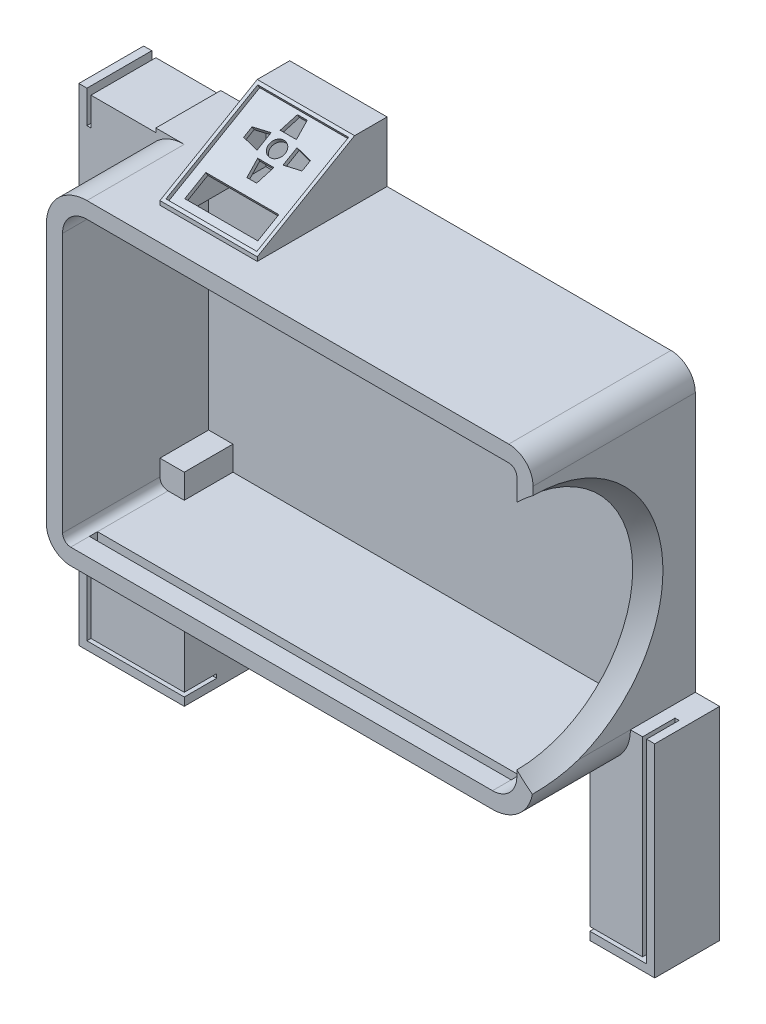
SolidWorks part; units mm, degrees
ref_plane "Front Plane" through (0, 0, 0) normal (0, 0, 1) x (1, 0, 0)
ref_plane "Top Plane" through (0, 0, 0) normal (0, 1, 0) x (1, 0, 0)
ref_plane "Right Plane" through (0, 0, 0) normal (1, 0, 0) x (0, 0, -1)
sketch "Sketch1" plane through (0, 0, 0) normal (0, 0, 1) x (1, 0, 0)
  line L1 (-190.5, -127) -> (190.5, -127)
  line L2 (-190.5, -127) -> (-190.5, 127)
  line L3 (-190.5, 127) -> (190.5, 127)
  line L4 (190.5, -127) -> (190.5, 127)
  line L5 (-190.5, -127) -> (190.5, 127) construction
  line L6 (-190.5, 127) -> (190.5, -127) construction
  point P0 (0, 0)
  dimension "D1" = 381
  dimension "D2" = 254
extrude "Boss-Extrude1" add sketch "Sketch1" against normal blind 127
fillet "Fillet5" radius 19.05 2 edges at (-190.5, -127, -63.5) (190.5, 127, -63.5)
fillet "Fillet4" radius 31.75 2 edges at (190.5, -127, -63.5) (-190.5, 127, -63.5)
sketch "Sketch3" plane through (0, 0, 0) normal (0, 0, -1) x (-1, 0, 0)
  line L16 (-158.75, -114.3) -> (171.45, -114.3)
  line L17 (-177.8, 107.95) -> (-177.8, -95.25)
  line L18 (158.75, 114.3) -> (-171.45, 114.3)
  line L19 (177.8, -107.95) -> (177.8, 95.25)
  line L20 (-158.75, -114.3) -> (171.45, -114.3)
  line L21 (-177.8, 107.95) -> (-177.8, -95.25)
  line L22 (158.75, 114.3) -> (-171.45, 114.3)
  line L23 (177.8, -107.95) -> (177.8, 95.25)
  arc A13 (-177.8, -95.25) -> (-158.75, -114.3) centre (-158.75, -95.25) ccw
  arc A14 (-171.45, 114.3) -> (-177.8, 107.95) centre (-171.45, 107.95) ccw
  arc A15 (177.8, 95.25) -> (158.75, 114.3) centre (158.75, 95.25) ccw
  arc A16 (171.45, -114.3) -> (177.8, -107.95) centre (171.45, -107.95) ccw
  arc A17 (-177.8, -95.25) -> (-158.75, -114.3) centre (-158.75, -95.25) ccw
  arc A18 (-171.45, 114.3) -> (-177.8, 107.95) centre (-171.45, 107.95) ccw
  arc A19 (177.8, 95.25) -> (158.75, 114.3) centre (158.75, 95.25) ccw
  arc A20 (171.45, -114.3) -> (177.8, -107.95) centre (171.45, -107.95) ccw
  dimension "D1" = 12.7
extrude "Cut-Extrude1" cut sketch "Sketch3" along normal offset from surface (114.3 mm away) 12.7 up to face at (0, 0, -127)
sketch "Sketch5" plane through (0, -127, 0) normal (0, -1, 0) x (1, 0, 0)
  line L0 (158.75, -127) -> (158.75, 0) construction
  line L1 (158.75, -14.605) -> (-171.45, -14.605)
  line L2 (158.75, -14.605) -> (158.75, -20.955)
  line L3 (158.75, -20.955) -> (-171.45, -20.955)
  line L4 (-171.45, -14.605) -> (-171.45, -20.955)
  line L5 (-171.45, 0) -> (-171.45, -127) construction
  line L6 (-171.45, 0) -> (158.75, 0) construction
  dimension "D1" = 6.35
  dimension "D2" = 14.605
extrude "Cut-Extrude2" cut sketch "Sketch5" against normal up to next
ref_plane "Plane1" through (0, 0, 0) normal (0, 1, 0) x (1, 0, 0)
sketch "Sketch6" plane through (0, 0, 0) normal (0, 1, 0) x (1, 0, 0)
  line L0 (139.7, 0) -> (266.7, 0)
  line L1 (171.45, 0) -> (-158.75, 0) construction
  line L2 (266.7, 0) -> (266.7, 127)
  line L3 (171.45, 127) -> (-158.75, 127) construction
  line L4 (190.5, 127) -> (190.5, 0) construction
  arc A0 (139.7, 0) -> (266.7, 127) centre (266.7, 0) cw
  point P7 (277.1595, 123.7315)
  point P10 (248.6882, 127)
  point P13 (139.7, 0)
  point P14 (0, 0)
  dimension "D1" = 76.2
revolve "Cut-Revolve1" cut sketch "Sketch6" angle 360 about L2
sketch "Sketch7" plane through (0, 0, -127) normal (0, 0, -1) x (-1, 0, 0)
  line L0 (190.5, 95.25) -> (190.5, -107.95) construction
  line L1 (158.75, 127) -> (241.3, 127)
  line L2 (158.75, 127) -> (158.75, 50.8)
  line L3 (158.75, 50.8) -> (241.3, 50.8)
  line L4 (241.3, 127) -> (241.3, 50.8)
  line L5 (171.45, -127) -> (-158.75, -127) construction
  line L6 (234.95, 127) -> (231.775, 127)
  line L7 (234.95, 127) -> (234.95, 101.6)
  line L8 (234.95, 101.6) -> (231.775, 101.6)
  line L9 (231.775, 127) -> (231.775, 101.6)
  line L10 (-158.75, -95.25) -> (-209.55, -95.25)
  line L11 (-158.75, -95.25) -> (-158.75, -254)
  line L12 (-158.75, -254) -> (-209.55, -254)
  line L13 (-209.55, -95.25) -> (-209.55, -254)
  line L14 (0, 127) -> (0, -127) construction
  line L15 (-171.45, 127) -> (158.75, 127) construction
  line L16 (158.75, -254) -> (241.3, -254)
  line L17 (241.3, -95.25) -> (241.3, -254)
  line L18 (158.75, -95.25) -> (241.3, -95.25)
  line L19 (158.75, -95.25) -> (158.75, -254)
  line L21 (231.775, 127) -> (180.975, 127)
  line L22 (231.775, 127) -> (231.775, 123.825)
  line L23 (231.775, 123.825) -> (180.975, 123.825)
  line L24 (180.975, 127) -> (180.975, 123.825)
  point P31 (181.2865, 123.825)
  line M11 (190.5, -107.95) -> (190.5, 95.25)
  arc M12 (190.5, 95.25) -> (158.75, 127) centre (158.75, 95.25) ccw
  dimension "D1" = 50.8
  dimension "D2" = 76.2
  dimension "D3" = 3.175
  dimension "D4" = 6.35
  dimension "D5" = 25.4
  dimension "D6" = 50.8
  dimension "D7" = 127
  dimension "D8" = 50.8
extrude "Boss-Extrude2" add sketch "Sketch7" against normal blind 50.8 contours L9 L1 L3 L4 L7 L8 M12 M11 | L16 L17 L18 L19 | L11 L10 L13 L12 region at (-214.1054, 88.5803, -127)
sketch "Sketch8" plane through (0, 0, -76.2) normal (0, 0, 1) x (1, 0, 0)
  line L0 (-234.95, -95.25) -> (-234.95, -247.65)
  line L1 (-190.5, -95.25) -> (-241.3, -95.25) construction
  line L2 (-234.95, -247.65) -> (-158.75, -247.65)
  line L3 (-158.75, -127) -> (-158.75, -254) construction
  line L4 (-158.75, -247.65) -> (-158.75, -244.475)
  line L5 (-158.75, -244.475) -> (-231.775, -244.475)
  line L6 (-231.775, -244.475) -> (-231.775, -95.25)
  line L7 (-231.775, -95.25) -> (-234.95, -95.25)
  line L8 (-234.95, 101.6) -> (-231.775, 101.6) construction
  line L9 (-234.95, 127) -> (-234.95, 101.6) construction
  line L10 (-158.75, -254) -> (-241.3, -254) construction
  line L11 (158.75, -247.65) -> (203.2, -247.65)
  line L12 (158.75, -127) -> (158.75, -254) construction
  line L13 (203.2, -247.65) -> (203.2, -95.25)
  line L14 (190.5, -95.25) -> (209.55, -95.25) construction
  line L15 (203.2, -95.25) -> (200.025, -95.25)
  line L16 (200.025, -95.25) -> (200.025, -244.475)
  line L17 (200.025, -244.475) -> (158.75, -244.475)
  line L18 (158.75, -244.475) -> (158.75, -247.65)
  line L19 (209.55, -95.25) -> (209.55, -254) construction
  point P26 (200.025, -95.25)
  point P27 (201.5135, -95.25)
  dimension "D1" = 6.35
  dimension "D2" = 6.35
extrude "Cut-Extrude3" cut sketch "Sketch8" against normal blind 25.4
ref_plane "Plane2" through (-127, 0, 0) normal (1, 0, 0) x (0, 0, -1)
sketch "Sketch9" plane through (-127, 0, 0) normal (1, 0, 0) x (0, 0, -1)
  line L0 (25.4, 127) -> (25.4, 130.175)
  line L1 (0, 127) -> (127, 127) construction
  line L2 (25.4, 130.175) -> (101.6, 174.1691)
  line L4 (25.4, 127) -> (127, 127)
  line L5 (0, 127) -> (0, 107.95) construction
  line L6 (101.6, 174.1691) -> (127, 174.1691)
  line L7 (127, 174.1691) -> (127, 127)
  line L8 (127, 107.95) -> (127, 127) construction
  point P4 (107.95, 174.4916)
  point P9 (101.6, 127)
  point P11 (0, 0)
  dimension "D1" = 25.4
  dimension "D3" = 25.4
  dimension "D4" = 3.175
  dimension "D5" = 60
extrude "Boss-Extrude3" add sketch "Sketch9" along normal blind 76.2
sketch "Sketch10" plane through (0, 86.6327, 50.0174) normal (0, 0.866, 0.5) x (1, 0, 0)
  line L8 (-124.46, 172.5327) -> (-124.46, 89.6245)
  line L9 (-124.46, 89.6245) -> (-53.34, 89.6245)
  line L10 (-53.34, 89.6245) -> (-53.34, 172.5327)
  line L11 (-53.34, 172.5327) -> (-124.46, 172.5327)
  line L12 (-124.46, 172.5327) -> (-124.46, 89.6245)
  line L13 (-124.46, 89.6245) -> (-53.34, 89.6245)
  line L14 (-53.34, 89.6245) -> (-53.34, 172.5327)
  line L15 (-53.34, 172.5327) -> (-124.46, 172.5327)
  dimension "D1" = 2.54
extrude "Cut-Extrude4" cut sketch "Sketch10" against normal blind 12.7
sketch "Sketch11" plane through (0, 114.3, 0) normal (0, -1, 0) x (1, 0, 0)
  line L0 (-124.46, -33.9497) -> (-53.34, -33.9497) construction
  line L1 (-124.46, -33.9497) -> (-53.34, -33.9497)
  line L2 (-124.46, -33.9497) -> (-124.46, -105.7503)
  line L3 (-124.46, -105.7503) -> (-53.34, -105.7503)
  line L4 (-53.34, -33.9497) -> (-53.34, -105.7503)
  line L5 (-124.46, -105.7503) -> (-124.46, -33.9497) construction
  line L6 (-53.34, -105.7503) -> (-124.46, -105.7503) construction
  line L7 (-53.34, -33.9497) -> (-53.34, -105.7503) construction
extrude "Cut-Extrude5" cut sketch "Sketch11" against normal up to surface (6.1465 mm away) up to face at (-88.9, 141.1735, -69.85)
ref_plane "Plane3" through (0, 83.8831, 48.4299) normal (0, 0.866, 0.5) x (1, 0, 0)
sketch "Sketch12" plane through (0, 83.8831, 48.4299) normal (0, 0.866, 0.5) x (1, 0, 0)
  line L0 (-53.34, 89.6245) -> (-53.34, 172.5327) construction
  line L1 (-124.46, 89.6245) -> (-53.34, 89.6245) construction
  line L2 (-124.46, 172.5327) -> (-124.46, 89.6245) construction
  line L3 (-53.34, 172.5327) -> (-124.46, 172.5327) construction
  line L4 (-53.34, 89.6245) -> (-53.34, 172.5327)
  line L5 (-124.46, 89.6245) -> (-53.34, 89.6245)
  line L6 (-124.46, 172.5327) -> (-124.46, 89.6245)
  line L7 (-53.34, 172.5327) -> (-124.46, 172.5327)
  line L8 (-88.9, 172.5327) -> (-88.9, 89.6245) construction
  line L9 (-82.55, 136.9727) -> (-95.25, 136.9727)
  line L10 (-78.74, 153.4827) -> (-66.04, 150.9427)
  line L11 (-78.74, 153.4827) -> (-78.74, 140.7827)
  line L12 (-78.74, 140.7827) -> (-66.04, 143.3227)
  line L13 (-66.04, 150.9427) -> (-66.04, 143.3227)
  line L14 (-82.55, 136.9727) -> (-85.09, 124.2727)
  line L15 (-85.09, 124.2727) -> (-92.71, 124.2727)
  line L16 (-95.25, 136.9727) -> (-92.71, 124.2727)
  line L17 (-99.06, 140.7827) -> (-99.06, 153.4827)
  line L18 (-99.06, 140.7827) -> (-111.76, 143.3227)
  line L19 (-111.76, 143.3227) -> (-111.76, 150.9427)
  line L20 (-99.06, 153.4827) -> (-111.76, 150.9427)
  line L21 (-95.25, 157.2927) -> (-82.55, 157.2927)
  line L22 (-95.25, 157.2927) -> (-92.71, 169.9927)
  line L23 (-92.71, 169.9927) -> (-85.09, 169.9927)
  line L24 (-82.55, 157.2927) -> (-85.09, 169.9927)
  line L26 (-116.84, 95.9745) -> (-59.69, 95.9745)
  line L27 (-116.84, 95.9745) -> (-116.84, 115.0245)
  line L28 (-116.84, 115.0245) -> (-59.69, 115.0245)
  line L29 (-59.69, 95.9745) -> (-59.69, 115.0245)
  circle A0 centre (-88.9, 147.1327) radius 6.35
  point P20 (-88.9, 153.4827)
  point P29 (-59.69, 114.3829)
  dimension "D1" = 12.7
  dimension "D2" = 12.7
  dimension "D3" = 10.16
  dimension "D4" = 7.62
  dimension "D5" = 12.7
  dimension "D6" = 25.4
  dimension "D8" = 57.15
  dimension "D9" = 19.05
  dimension "D10" = 6.35
  dimension "D11" = 6.35
  dimension "D7" = 4
extrude "Boss-Extrude4" add sketch "Sketch12" against normal blind 3.175
